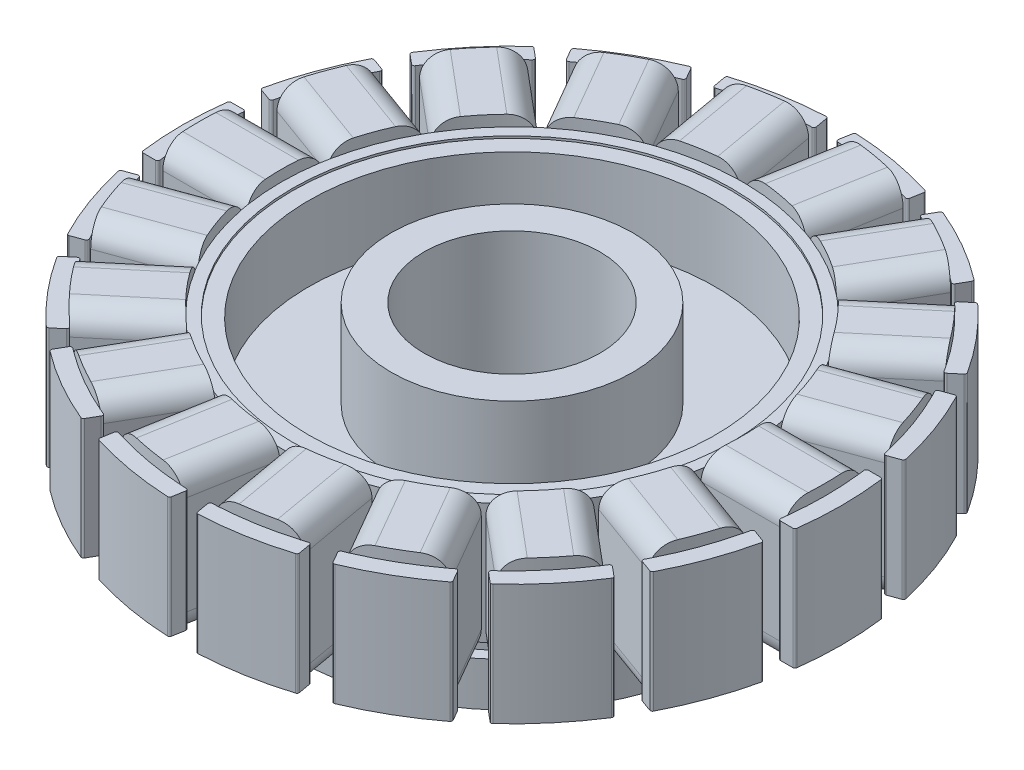
SolidWorks part; units mm, degrees
ref_plane "前视基准面" through (0, 0, 0) normal (0, 0, 1) x (1, 0, 0)
ref_plane "上视基准面" through (0, 0, 0) normal (0, 1, 0) x (1, 0, 0)
ref_plane "右视基准面" through (0, 0, 0) normal (1, 0, 0) x (0, 0, -1)
sketch "草图1" plane through (0, 0, 0) normal (0, 1, 0) x (1, 0, 0)
  circle A0 centre (0, 0) radius 20
  dimension "D1" = 40
extrude "凸台-拉伸1" add sketch "草图1" along normal blind 4
sketch "草图2" plane through (0, 0, 0) normal (0, -1, 0) x (-1, 0, 0)
  circle A0 centre (0, 0) radius 12.5
  dimension "D1" = 25
extrude "切除-拉伸1" cut sketch "草图2" against normal blind 1
chamfer "倒角1" distance 1 angle 45 1 edges at (0, 1, -12.5)
sketch "草图3" plane through (0, 4, 0) normal (0, 1, 0) x (1, 0, 0)
  circle A0 centre (0, 0) radius 19
  dimension "D1" = 38
extrude "凸台-拉伸2" add sketch "草图3" along normal blind 1
sketch "草图4" plane through (0, 5, 0) normal (0, 1, 0) x (1, 0, 0)
  circle A0 centre (0, 0) radius 21
  dimension "D1" = 42
extrude "凸台-拉伸3" add sketch "草图4" along normal blind 13
sketch "草图5" plane through (0, 18, 0) normal (0, 1, 0) x (1, 0, 0)
  line L0 (21, 0) -> (30, 0) construction
  line L1 (20.7063, -3.5) -> (28.2843, -3.5)
  line L2 (20.7063, 3.5) -> (28.2843, 3.5)
  line L3 (28.4473, -4) -> (29.5567, -4)
  line L4 (28.4473, 4) -> (29.5567, 4)
  line L5 (0, -4) -> (30, -4) construction
  line L6 (0, -3.5) -> (30, -3.5) construction
  line L7 (0, 0) -> (30, 0) construction
  line L8 (0, 3.5) -> (30, 3.5) construction
  line L9 (0, 4) -> (30, 4) construction
  arc A0 (29.7551, -3.8255) -> (29.7551, 3.8255) centre (0, 0) ccw
  circle A1 centre (0, 0) radius 21 construction
  arc A2 (20.7063, -3.5) -> (20.7063, 3.5) centre (0, 0) ccw
  arc A3 (28.2491, -3.7735) -> (28.2843, -3.5) centre (0, 0) ccw
  arc A4 (28.2843, 3.5) -> (28.2491, 3.7735) centre (0, 0) ccw
  arc A5 (28.2491, -3.7735) -> (28.4473, -4) centre (28.4473, -3.8) ccw
  arc A6 (29.7551, -3.8255) -> (29.5567, -4) centre (29.5567, -3.8) cw
  arc A7 (29.7551, 3.8255) -> (29.5567, 4) centre (29.5567, 3.8) ccw
  arc A8 (28.4473, 4) -> (28.2491, 3.7735) centre (28.4473, 3.8) ccw
  point P28 (28.2179, 4)
  dimension "D1" = 60
  dimension "D4" = 28.5
  dimension "D7" = 0.2
  dimension "D2" = 3.5
  dimension "D3" = 3.5
  dimension "D5" = 0.5
  dimension "D6" = 0.5
extrude "凸台-拉伸5" add sketch "草图5" against normal blind 13
fillet "圆角2" radius 2 4 edges at (24.4953, 5, 3.5) (24.4953, 5, -3.5) (24.4953, 18, -3.5) (24.4953, 18, 3.5)
pattern_circular "阵列(圆周)1" count 18 over 360 about axis through (0, 18, 0) along (0, -1, 0) of "圆角2", "凸台-拉伸5"
sketch "草图6" plane through (0, 18, 0) normal (0, 1, 0) x (1, 0, 0)
  circle A0 centre (0, 0) radius 30
  circle A1 centre (0, 0) radius 28.5
extrude "切除-拉伸2" cut sketch "草图6" against normal blind 1
sketch "草图7" plane through (0, 1, 0) normal (0, -1, 0) x (-1, 0, 0)
  circle A0 centre (0, 0) radius 8
  dimension "D1" = 16
extrude "切除-拉伸3" cut sketch "草图7" against normal blind 21
sketch "草图8" plane through (0, 18, 0) normal (0, 1, 0) x (1, 0, 0)
  circle A0 centre (0, 0) radius 18.5
  dimension "D1" = 37
extrude "切除-拉伸4" cut sketch "草图8" against normal blind 8
sketch "草图9" plane through (0, 10, 0) normal (0, 1, 0) x (1, 0, 0)
  circle A0 centre (0, 0) radius 11
  circle A1 centre (0, 0) radius 8 construction
  circle A2 centre (0, 0) radius 8
  dimension "D1" = 22
extrude "凸台-拉伸6" add sketch "草图9" along normal blind 8
sketch "草图10" plane through (0, 0, 0) normal (0, -1, 0) x (-1, 0, 0)
  line L1 (11, -11) -> (-11, -11) construction
  line L2 (11, -11) -> (11, 11) construction
  line L3 (11, 11) -> (-11, 11) construction
  line L4 (-11, -11) -> (-11, 11) construction
  line L5 (11, -11) -> (-11, 11) construction
  line L6 (11, 11) -> (-11, -11) construction
  point P0 (0, 0)
  dimension "D1" = 22
  dimension "D2" = 22
hole_wizard "M3 螺纹孔1" positions "草图11" profile "草图12" tap size "M3" standard "GB"
sketch "草图11" plane through (0, 0, 0) normal (0, -1, 0) x (-1, 0, 0)
  point P0 (11, -11)
  point P3 (-11, -11)
  point P6 (-11, 11)
  point P9 (11, 11)
sketch "草图12" plane through (-11, 0, 11) normal (1, 0, 0) x (0, 0, -1)
  line L0 (0, 0) -> (0, 8.2511)
  line L1 (0, 8.2511) -> (1.25, 7.5)
  line L2 (1.25, 7.5) -> (1.25, 0)
  line L5 (1.25, 0) -> (0, 0)
  line L10 (0, 8.2511) -> (-1.25, 7.5) construction
  line L11 (0, -6.35) -> (0, 107.95) construction
  dimension "螺纹孔钻头直径" = 2.5
  dimension "螺纹孔钻头深度" = 7.5
  dimension "导头角度" = 118
cosmetic thread "孔螺蚊线1" parameters "D1"=6, "D2"=3
cosmetic thread "孔螺蚊线2" parameters "D1"=6, "D2"=3
cosmetic thread "孔螺蚊线3" parameters "D1"=6, "D2"=3
cosmetic thread "孔螺蚊线4" parameters "D1"=6, "D2"=3
sketch "草图13" plane through (0, 18, 0) normal (0, 1, 0) x (1, 0, 0)
  circle A0 centre (0, 0) radius 21
  circle A1 centre (0, 0) radius 18.5
extrude "切除-拉伸5" cut sketch "草图13" against normal blind 1
sketch "草图14" plane through (0, 17, 0) normal (0, 1, 0) x (1, 0, 0)
  circle A0 centre (0, 0) radius 20
  circle A1 centre (0, 0) radius 18.5
  dimension "D1" = 40
extrude "切除-拉伸6" cut sketch "草图14" against normal blind 0.2
sketch "草图15" plane through (0, 5, 0) normal (0, -1, 0) x (-1, 0, 0)
  circle A0 centre (0, 0) radius 30
  circle A1 centre (0, 0) radius 28.5
extrude "切除-拉伸7" cut sketch "草图15" against normal blind 1
sketch "草图16" plane through (0, 5, 0) normal (0, -1, 0) x (-1, 0, 0)
  circle A0 centre (0, 0) radius 21
  circle A1 centre (0, 0) radius 19.576
extrude "切除-拉伸8" cut sketch "草图16" against normal blind 1
